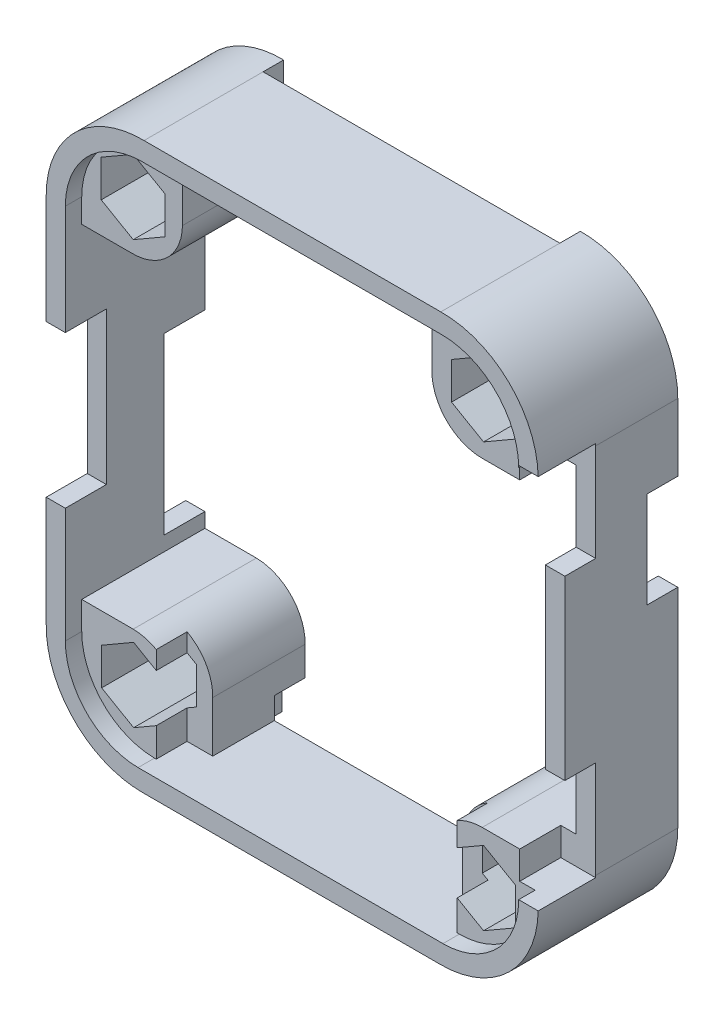
SolidWorks part; units mm, degrees
ref_plane "前视基准面" through (0, 0, 0) normal (0, 0, 1) x (1, 0, 0)
ref_plane "上视基准面" through (0, 0, 0) normal (0, 1, 0) x (1, 0, 0)
ref_plane "右视基准面" through (0, 0, 0) normal (1, 0, 0) x (0, 0, -1)
sketch "Model" plane through (0, 0, 0) normal (0, 0, 1) x (1, 0, 0)
  line L0 (30.9788, -1.8859) -> (34.0965, -3.6859)
  line L1 (30.9788, -1.8859) -> (30.9788, 1.7141)
  line L2 (30.9788, 1.7141) -> (34.0965, 3.5141)
  line L3 (34.0965, 3.5141) -> (37.2142, 1.7141)
  line L4 (37.2142, -1.8859) -> (37.2142, 1.7141)
  line L5 (34.0965, -3.6859) -> (37.2142, -1.8859)
  line L6 (-3.1177, -1.8) -> (0, -3.6)
  line L7 (-3.1177, -1.8) -> (-3.1177, 1.8)
  line L8 (-3.1177, 1.8) -> (0, 3.6)
  line L9 (0, 3.6) -> (3.1177, 1.8)
  line L10 (3.1177, -1.8) -> (3.1177, 1.8)
  line L11 (0, -3.6) -> (3.1177, -1.8)
  line L12 (30.9788, 39.3637) -> (34.0965, 37.5637)
  line L13 (30.9788, 39.3637) -> (30.9788, 42.9637)
  line L14 (30.9788, 42.9637) -> (34.0965, 44.7637)
  line L15 (34.0965, 44.7637) -> (37.2142, 42.9637)
  line L16 (37.2142, 39.3637) -> (37.2142, 42.9637)
  line L17 (34.0965, 37.5637) -> (37.2142, 39.3637)
  line L18 (-0.0411, 44.7637) -> (3.0766, 42.9637)
  line L19 (3.0766, 39.3637) -> (3.0766, 42.9637)
  line L20 (-0.0411, 37.5637) -> (3.0766, 39.3637)
  line L21 (-3.1588, 39.3637) -> (-0.0411, 37.5637)
  line L22 (-3.1588, 39.3637) -> (-3.1588, 42.9637)
  line L23 (-3.1588, 42.9637) -> (-0.0411, 44.7637)
  line L24 (29.0273, -5.152) -> (29.0273, 0.0315)
  line L25 (33.9694, 4.9693) -> (39.1228, 4.9693)
  line L26 (4.7086, -5.152) -> (4.7086, -0.2062)
  line L27 (-5.0568, 4.6956) -> (-0.0405, 4.6956)
  line L28 (34.0629, 36.116) -> (39.1228, 36.116)
  line L29 (29.0634, 41.0191) -> (29.0634, 46.1786)
  line L30 (4.7571, 41.1487) -> (4.7571, 46.1786)
  line L31 (-5.0568, 36.3496) -> (-0.2126, 36.3496)
  line L32 (30.1286, 46.1932) -> (30.1286, 48.0554)
  line L33 (3.7576, 46.1786) -> (3.7576, 48.0554)
  line L34 (39.1228, 2.2293) -> (39.1228, 3.8624)
  line L36 (39.1228, 3.8624) -> (39.1228, 38.6943)
  line L37 (2.0336, -5.152) -> (31.7416, -5.152)
  line L38 (-5.0568, 1.9858) -> (-5.0568, 38.6786)
  line L39 (2.4432, 46.1786) -> (31.6072, 46.1786)
  line L40 (-6.9179, 28.0099) -> (-5.0568, 28.0099)
  line L41 (-6.9179, 13.1913) -> (-5.0568, 13.1913)
  line L42 (39.1228, 38.6943) -> (41.0242, 38.6943)
  line L43 (30.09, -7.0389) -> (30.09, -5.152)
  line L44 (3.7622, -7.0389) -> (3.7622, -5.152)
  line L45 (-6.9179, 6.6127) -> (-5.0568, 6.6127)
  line L46 (-6.9179, 23.1227) -> (-5.0568, 23.1227)
  line L47 (41.0242, 2.4471) -> (41.0242, 38.6943)
  line L48 (2.4491, -7.0389) -> (31.5381, -7.0389)
  line L49 (-6.9179, 2.4542) -> (-6.9179, 38.6999)
  line L50 (2.6141, 48.0554) -> (31.5311, 48.0554)
  line L51 (39.1228, 32.3281) -> (41.0242, 32.3281)
  line L52 (39.1228, 22.5621) -> (41.0242, 22.5621)
  line L53 (41.0242, 2.4471) -> (39.1228, 2.4471)
  arc A106 (33.9694, 4.9693) -> (29.0273, 0.0315) centre (33.9673, 0.0293) ccw
  arc A109 (4.7086, -0.2062) -> (-0.0405, 4.6956) centre (-0.1168, -0.1298) ccw
  arc A112 (29.0634, 41.0191) -> (34.0629, 36.116) centre (33.9674, 41.0191) ccw
  arc A115 (-0.2126, 36.3496) -> (4.7571, 41.1487) centre (-0.1045, 41.2104) ccw
  arc A118 (-5.0568, 1.9858) -> (2.0336, -5.152) centre (2.0811, 1.9858) ccw
  arc A121 (31.7416, -5.152) -> (39.1228, 2.2293) centre (31.7416, 2.2293) ccw
  arc A124 (39.1228, 38.6943) -> (31.6072, 46.1786) centre (31.6228, 38.6787) ccw
  arc A127 (2.4432, 46.1786) -> (-5.0568, 38.6786) centre (2.4432, 38.6786) ccw
  arc A130 (31.5381, -7.0389) -> (41.0242, 2.4471) centre (31.5381, 2.4472) ccw
  arc A133 (-6.9179, 2.4542) -> (2.4491, -7.0389) centre (2.4483, 2.3281) ccw
  arc A136 (41.0242, 38.6943) -> (31.5311, 48.0554) centre (31.6573, 38.6892) ccw
  arc A139 (2.6141, 48.0554) -> (-6.9179, 38.6999) centre (2.4481, 38.6908) ccw
  point P39 (39.1228, 38.6943)
  point P42 (41.0242, 38.6943)
extrude "凸台-拉伸1" add sketch "Model" along normal blind 12 contours L39 A127 L38 L31 A115 L30 L22 L23 L18 L19 L20 L21 region at (-4.9179, 37.5141, 0)
extrude "凸台-拉伸2" add sketch "Model<3>" along normal blind 12 separate body contours L38 A118 L37 L26 A109 L27 L11 L6 L7 L8 L9 L10 | L37 A121 L34 L36 L25 A106 L24 L5 L0 L1 L2 L3 L4 | L36 A124 L39 L29 A112 L28 L17 L12 L13 L14 L15 L16 region at (29.1702, -2.5602, 0) region at (4.2354, -5.0133, 0) region at (36.5928, 36.2583, 0)
sketch "Model<3>" plane through (0, 0, 0) normal (0, 0, 1) x (1, 0, 0) same geometry as "Model"
extrude "凸台-拉伸3" add sketch "Model<4>" along normal blind 13.6 contours L49 A133 L48 L44 L37 A118 L38 L45 | L50 A139 L49 L40 L38 A127 L39 L33 | L48 A130 L53 L34 A121 L37 L43 | L42 A136 L50 L33 L39 A124 | L36 L51 L47 L42 | L36 L52 L47 L51 | L53 L47 L52 L36 L34 | L49 L46 L38 L40 | L49 L41 L38 L46 | L49 L45 L38 L41 | L44 L48 L43 L37 region at (16.9261, -6.0954, 0) region at (30.9158, -5.2967, 0) region at (3.5889, -6.0954, 0) region at (40.0735, 12.5046, 0) region at (40.0735, 27.4451, 0) region at (40.0735, 35.5112, 0) region at (-5.9873, 9.902, 0) region at (-5.9873, 18.157, 0) region at (37.1862, 44.2653, 0) region at (-5.9873, 25.5663, 0) region at (-5.9873, 28.237, 0)
sketch "Model<4>" plane through (0, 0, 0) normal (0, 0, 1) x (1, 0, 0) same geometry as "Model"
extrude "切除-拉伸1" cut sketch "Model<6>" along normal blind 4 contours L49 L45 L38 L41 | L49 L41 L38 L46 region at (-5.9873, 9.902, 0) region at (-5.9873, 18.157, 0)
sketch "Model<6>" plane through (0, 0, 0) normal (0, 0, 1) x (1, 0, 0) same geometry as "Model"
extrude "凸台-拉伸5" add sketch "Model<7>" along normal blind 16 contours L49 L46 L38 L40 | L49 L41 L38 L46 region at (-5.9873, 18.157, 0) region at (-5.9873, 25.5663, 0)
sketch "Model<7>" plane through (0, 0, 0) normal (0, 0, 1) x (1, 0, 0) same geometry as "Model"
extrude "切除-拉伸2" cut sketch "Model<8>" along normal blind 4 contours L49 L41 L38 L46 region at (-5.9873, 18.157, 0)
sketch "Model<8>" plane through (0, 0, 0) normal (0, 0, 1) x (1, 0, 0) same geometry as "Model"
sketch "草图3" plane through (0, 0, 16) normal (0, 0, 1) x (1, 0, 0)
  line L1 (-6.9179, 28.0099) -> (-5.0568, 28.0099)
  line L2 (-6.9179, 28.0099) -> (-6.9179, 13.1913)
  line L3 (-6.9179, 13.1913) -> (-5.0568, 13.1913)
  line L4 (-5.0568, 28.0099) -> (-5.0568, 13.1913)
extrude "切除-拉伸3" cut sketch "草图3" against normal blind 6.4
extrude "凸台-拉伸6" add sketch "Model<11>" along normal blind 16 contours L36 L51 L47 L42 | L36 L52 L47 L51 | L53 L47 L52 L36 L34 region at (40.0735, 12.5046, 0) region at (40.0735, 27.4451, 0) region at (40.0735, 35.5112, 0)
sketch "Model<11>" plane through (0, 0, 0) normal (0, 0, 1) x (1, 0, 0) same geometry as "Model"
extrude "切除-拉伸5" cut sketch "Model<12>" along normal blind 3 contours L36 L52 L47 L51 region at (40.0735, 27.4451, 0)
sketch "Model<12>" plane through (0, 0, 0) normal (0, 0, 1) x (1, 0, 0) same geometry as "Model"
sketch "草图4" plane through (0, 0, 16) normal (0, 0, 1) x (1, 0, 0)
  line L1 (41.0242, 2.4471) -> (39.1228, 2.4471)
  line L2 (41.0242, 2.4471) -> (41.0242, 38.6943)
  line L3 (41.0242, 38.6943) -> (39.1228, 38.6943)
  line L4 (39.1228, 2.4471) -> (39.1228, 38.6943)
extrude "切除-拉伸6" cut sketch "草图4" against normal blind 8
sketch "草图5" plane through (39.1228, 0, 0) normal (1, 0, 0) x (0, 0, -1)
  line L1 (-12, 36.116) -> (-8, 36.116)
  line L2 (-12, 36.116) -> (-12, 38.6943)
  line L3 (-12, 38.6943) -> (-8, 38.6943)
  line L4 (-8, 36.116) -> (-8, 38.6943)
extrude "切除-拉伸8" cut sketch "草图5" against normal blind 1.5
sketch "草图6" plane through (39.1228, 0, 0) normal (1, 0, 0) x (0, 0, -1)
  line L1 (-12, 2.4471) -> (-8, 2.4471)
  line L2 (-12, 2.4471) -> (-12, 4.9693)
  line L3 (-12, 4.9693) -> (-8, 4.9693)
  line L4 (-8, 2.4471) -> (-8, 4.9693)
extrude "切除-拉伸9" cut sketch "草图6" against normal blind 1.5
sketch "草图7" plane through (0, 0, 8) normal (0, 0, 1) x (1, 0, 0)
  line L0 (41.0242, 2.4471) -> (41.0242, 38.6943) construction
  line L1 (37.6228, 2.4471) -> (41.0242, 2.4471)
  line L2 (37.6228, 2.4471) -> (37.6228, 11.9471)
  line L3 (37.6228, 11.9471) -> (41.0242, 11.9471)
  line L4 (41.0242, 2.4471) -> (41.0242, 11.9471)
  line L5 (39.1228, 36.116) -> (39.1228, 4.9693) construction
  line L6 (37.6228, 38.6943) -> (41.0242, 38.6943)
  line L7 (37.6228, 38.6943) -> (37.6228, 29.1943)
  line L8 (37.6228, 29.1943) -> (41.0242, 29.1943)
  line L9 (41.0242, 38.6943) -> (41.0242, 29.1943)
  line L11 (41.0242, 11.9471) -> (39.1228, 11.9471)
  line L12 (41.0242, 11.9471) -> (41.0242, 29.1943)
  line L13 (41.0242, 29.1943) -> (39.1228, 29.1943)
  line L14 (39.1228, 11.9471) -> (39.1228, 29.1943)
  point P12 (39.1228, 29.1943)
  dimension "D1" = 9.5
  dimension "D2" = 9.5
extrude "凸台-拉伸7" add sketch "草图7" along normal blind 3 contours L8 L5 L3 L0 region at (40.0735, 20.5707, 8)
sketch "草图11" plane through (0, -7.0389, 0) normal (0, -1, 0) x (-1, 0, 0)
  line L0 (-31.5381, -13.6) -> (-31.5381, 0) construction
  line L1 (-2.4491, 0) -> (-31.5381, 0)
  line L2 (-2.4491, 0) -> (-2.4491, -3)
  line L3 (-2.4491, -3) -> (-31.5381, -3)
  line L4 (-31.5381, 0) -> (-31.5381, -3)
  dimension "D1" = 3
extrude "切除-拉伸15" cut sketch "草图11" against normal blind 4
sketch "草图12" plane through (0, 48.0554, 0) normal (0, 1, 0) x (1, 0, 0)
  line L0 (31.5311, -13.6) -> (31.5311, 0) construction
  line L1 (2.6141, 0) -> (31.5311, 0)
  line L2 (2.6141, 0) -> (2.6141, -2)
  line L3 (2.6141, -2) -> (31.5311, -2)
  line L4 (31.5311, 0) -> (31.5311, -2)
  dimension "D1" = 2
extrude "切除-拉伸16" cut sketch "草图12" against normal blind 3
sketch "草图13" plane through (0, 0, 12) normal (0, 0, 1) x (1, 0, 0)
  line L1 (4.7086, -5.152) -> (3.7086, -5.152)
  line L2 (4.7086, -5.152) -> (4.7086, 5.8044)
  line L3 (4.7086, 5.8044) -> (3.7086, 5.8044)
  line L4 (3.7086, -5.152) -> (3.7086, 5.8044)
  dimension "D1" = 1
extrude "切除-拉伸17" cut sketch "草图13" against normal blind 3
sketch "草图14" plane through (0, 0, 12) normal (0, 0, 1) x (1, 0, 0)
  line L1 (29.0273, -5.152) -> (30.0273, -5.152)
  line L2 (29.0273, -5.152) -> (29.0273, 8.1987)
  line L3 (29.0273, 8.1987) -> (30.0273, 8.1987)
  line L4 (30.0273, -5.152) -> (30.0273, 8.1987)
  dimension "D1" = 1
extrude "切除-拉伸19" cut sketch "草图14" against normal blind 3
sketch "草图16" plane through (0, 0, 0) normal (0, 0, -1) x (-1, 0, 0)
  line L1 (-29.0634, 45.0554) -> (-30.0634, 45.0554)
  line L2 (-29.0634, 45.0554) -> (-29.0634, 36.2476)
  line L3 (-29.0634, 36.2476) -> (-30.0634, 36.2476)
  line L4 (-30.0634, 45.0554) -> (-30.0634, 36.2476)
  dimension "D1" = 1
extrude "切除-拉伸23" cut sketch "草图16" against normal blind 2
sketch "草图17" plane through (0, 0, 0) normal (0, 0, -1) x (-1, 0, 0)
  line L1 (-4.7571, 45.0554) -> (-3.7571, 45.0554)
  line L2 (-4.7571, 45.0554) -> (-4.7571, 35.2986)
  line L3 (-4.7571, 35.2986) -> (-3.7571, 35.2986)
  line L4 (-3.7571, 45.0554) -> (-3.7571, 35.2986)
  dimension "D1" = 1
extrude "切除-拉伸24" cut sketch "草图17" against normal blind 2
sketch "草图18" plane through (4.7086, 0, 0) normal (-1, 0, 0) x (0, 0, 1)
  line L1 (9, -0.0535) -> (12, -0.0535)
  line L2 (9, -0.0535) -> (9, -0.2062)
  line L3 (9, -0.2062) -> (12, -0.2062)
  line L4 (12, -0.0535) -> (12, -0.2062)
extrude "切除-拉伸25" cut sketch "草图18" against normal blind 1
sketch "草图20" plane through (30.0273, 0, 0) normal (-1, 0, 0) x (0, 0, 1)
  line L1 (12, -5.152) -> (9, -5.152)
  line L2 (12, -5.152) -> (12, 5.6692)
  line L3 (12, 5.6692) -> (9, 5.6692)
  line L4 (9, -5.152) -> (9, 5.6692)
extrude "切除-拉伸27" cut sketch "草图20" against normal blind 1
sketch "草图21" plane through (3.7086, 0, 0) normal (1, 0, 0) x (0, 0, -1)
  line L1 (-9, -5.152) -> (-12, -5.152)
  line L2 (-9, -5.152) -> (-9, 5.6854)
  line L3 (-9, 5.6854) -> (-12, 5.6854)
  line L4 (-12, -5.152) -> (-12, 5.6854)
extrude "切除-拉伸28" cut sketch "草图21" against normal blind 1
extrude "切除-拉伸29" cut sketch "草图21<2>" against normal blind 1.5
sketch "草图21<2>" plane through (3.7086, 0, 0) normal (1, 0, 0) x (0, 0, -1) same geometry as "草图21"
extrude "切除-拉伸30" cut sketch "草图20<2>" against normal blind 1.5
sketch "草图20<2>" plane through (30.0273, 0, 0) normal (-1, 0, 0) x (0, 0, 1) same geometry as "草图20"
sketch "草图22" plane through (0, 6.6127, 0) normal (0, 1, 0) x (1, 0, 0)
  line L1 (-5.0568, -4) -> (-6.9179, -4)
  line L2 (-5.0568, -4) -> (-5.0568, 0)
  line L3 (-5.0568, 0) -> (-6.9179, 0)
  line L4 (-6.9179, -4) -> (-6.9179, 0)
extrude "切除-拉伸31" cut sketch "草图22" against normal blind 0.5
sketch "草图23" plane through (0, 2.4471, 0) normal (0, 1, 0) x (1, 0, 0)
  line L0 (41.0242, -13.6) -> (41.0242, -8)
  line L1 (41.0242, -8) -> (37.6228, -8)
  line L2 (37.6228, -8) -> (37.6228, -12)
  line L3 (37.6228, -12) -> (39.1228, -12)
  line L4 (39.1228, -12) -> (39.1228, -13.6)
  line L5 (39.1228, -13.6) -> (41.0242, -13.6)
extrude "切除-拉伸32" cut sketch "草图23" against normal blind 0.2
sketch "草图24" plane through (0, 38.6943, 0) normal (0, -1, 0) x (1, 0, 0)
  line L0 (39.1228, 13.6) -> (41.0242, 13.6)
  line L1 (41.0242, 13.6) -> (41.0242, 8)
  line L2 (41.0242, 8) -> (37.6228, 8)
  line L3 (37.6228, 8) -> (37.6228, 12)
  line L4 (37.6228, 12) -> (39.1228, 12)
  line L5 (39.1228, 12) -> (39.1228, 13.6)
extrude "切除-拉伸33" cut sketch "草图24" against normal blind 0.2
sketch "草图25" plane through (0, 22.5621, 0) normal (0, 1, 0) x (1, 0, 0)
  line L1 (41.0242, -3) -> (39.1228, -3)
  line L2 (41.0242, -3) -> (41.0242, 0)
  line L3 (41.0242, 0) -> (39.1228, 0)
  line L4 (39.1228, -3) -> (39.1228, 0)
extrude "凸台-拉伸8" add sketch "草图25" along normal blind 0.2
sketch "草图26" plane through (0, 32.3281, 0) normal (0, -1, 0) x (1, 0, 0)
  line L1 (39.1228, 3) -> (41.0242, 3)
  line L2 (39.1228, 3) -> (39.1228, 0)
  line L3 (39.1228, 0) -> (41.0242, 0)
  line L4 (41.0242, 3) -> (41.0242, 0)
extrude "凸台-拉伸9" add sketch "草图26" along normal blind 0.2
